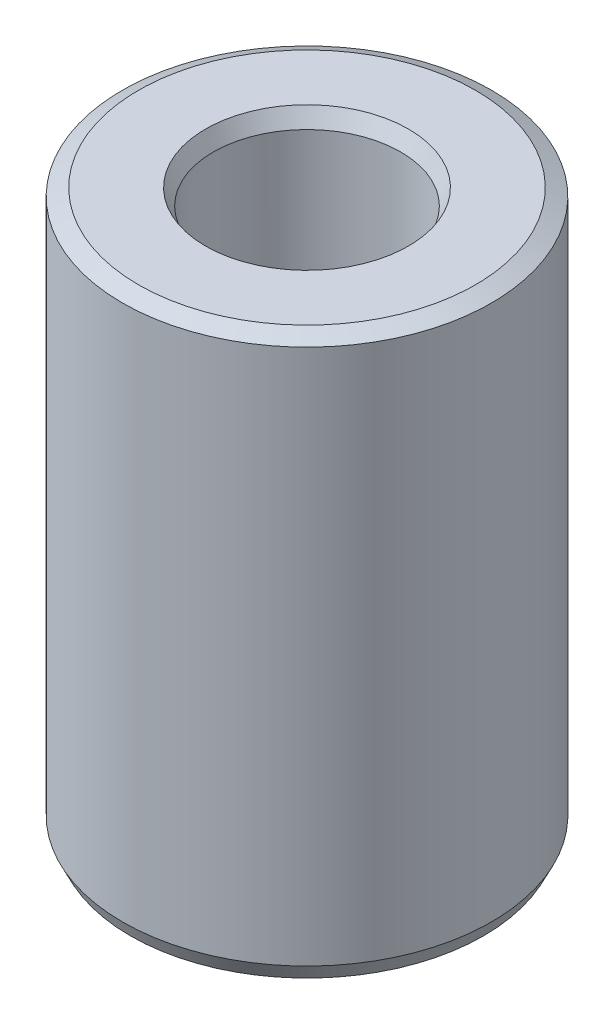
SolidWorks part; units mm, degrees
ref_plane "Front Plane" through (0, 0, 0) normal (0, 0, 1) x (1, 0, 0)
ref_plane "Top Plane" through (0, 0, 0) normal (0, 1, 0) x (1, 0, 0)
ref_plane "Right Plane" through (0, 0, 0) normal (1, 0, 0) x (0, 0, -1)
sketch "Sketch1" plane through (0, 0, 0) normal (0, 1, 0) x (1, 0, 0)
  circle A0 centre (0, 0) radius 25
  dimension "SLEEVE_OD" = 50
extrude "Boss-Extrude1" add sketch "Sketch1" along normal blind 75.8702
sketch "Sketch2" plane through (0, 0, 0) normal (0, 1, 0) x (1, 0, 0)
  circle A0 centre (0, 0) radius 12.6887
  dimension "BORE_D" = 25.3774
extrude "Cut-Extrude1" cut sketch "Sketch2" along normal through all
chamfer "Chamfer1" distance 1.0604 angle 63.854 4 edges at (0, 75.8702, 12.6887) (0, 0, 12.6887) (0, 0, 25) (0, 75.8702, 25) first distance on face at (0, 75.8702, 12.6887) first distance on face at (0, 0, 12.6887) first distance on face at (0, 75.8702, 25)
